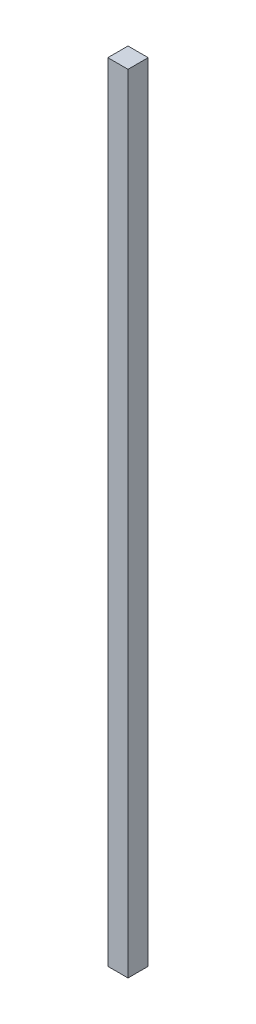
SolidWorks part; units mm, degrees
ref_plane "Front Plane" through (0, 0, 0) normal (0, 0, 1) x (1, 0, 0)
ref_plane "Top Plane" through (0, 0, 0) normal (0, 1, 0) x (1, 0, 0)
ref_plane "Right Plane" through (0, 0, 0) normal (1, 0, 0) x (0, 0, -1)
sketch "Sketch1" plane through (0, 0, 0) normal (0, 1, 0) x (1, 0, 0)
  line L1 (-6.35, -6.35) -> (6.35, -6.35)
  line L2 (-6.35, -6.35) -> (-6.35, 6.35)
  line L3 (-6.35, 6.35) -> (6.35, 6.35)
  line L4 (6.35, -6.35) -> (6.35, 6.35)
  line L5 (-6.35, -6.35) -> (6.35, 6.35) construction
  line L6 (-6.35, 6.35) -> (6.35, -6.35) construction
  point P0 (0, 0)
  dimension "D1" = 12.7
extrude "Boss-Extrude1" add sketch "Sketch1" along normal mid plane 495.3
